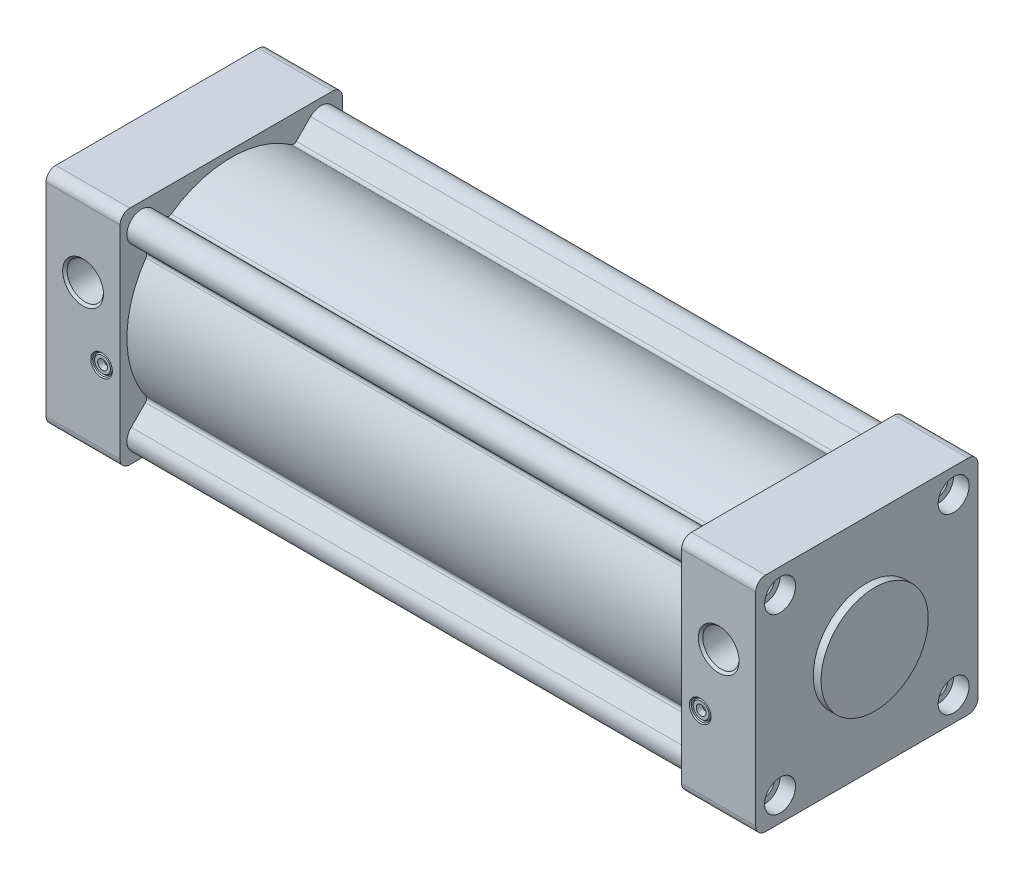
SolidWorks part; units mm, degrees
material "A3钢"
ref_plane "前视基准面" through (0, 0, 0) normal (0, 0, 1) x (1, 0, 0)
ref_plane "上视基准面" through (0, 0, 0) normal (0, 1, 0) x (1, 0, 0)
ref_plane "右视基准面" through (0, 0, 0) normal (1, 0, 0) x (0, 0, -1)
sketch "草图1" plane through (0, 0, 0) normal (1, 0, 0) x (0, 0, -1)
  line L0 (-52, -57) -> (52, -57)
  line L1 (57, -52) -> (57, 52)
  line L2 (52, 57) -> (-52, 57)
  line L3 (-57, 52) -> (-57, -52)
  arc A0 (-57, -52) -> (-52, -57) centre (-52, -52) ccw
  arc A1 (52, -57) -> (57, -52) centre (52, -52) ccw
  arc A2 (57, 52) -> (52, 57) centre (52, 52) ccw
  arc A3 (-52, 57) -> (-57, 52) centre (-52, 52) ccw
extrude "凸台-拉伸1" add sketch "草图1" along normal blind 38
sketch "草图2" plane through (0, 0, 0) normal (0, 1, 0) x (1, 0, 0)
  line L0 (-20, 0) -> (-20, 23)
  line L1 (-19, 24) -> (-5, 24)
  line L2 (-5, 24) -> (-5, 26.5)
  line L3 (-4, 27.5) -> (38, 27.5)
  line L4 (38, 27.5) -> (38, 0)
  line L5 (38, 0) -> (-20, 0)
  line L6 (38, 0) -> (-20, 0) construction
  arc A0 (-20, 23) -> (-19, 24) centre (-19, 23) cw
  arc A1 (-5, 26.5) -> (-4, 27.5) centre (-4, 26.5) cw
revolve "旋转1" add sketch "草图2" angle 360 about L6
ref_plane "基准面1" through (38, 0, 0) normal (1, 0, 0) x (0, 0, -1)
sketch "草图3" plane through (38, 0, 0) normal (1, 0, 0) x (0, 0, -1)
  line L0 (-43.9685, -33.3619) -> (-51.3033, -40.6967)
  line L1 (-40.6967, -51.3033) -> (-33.3619, -43.9685)
  line L2 (33.3619, -43.9685) -> (40.6967, -51.3033)
  line L3 (51.3033, -40.6967) -> (43.9685, -33.3619)
  line L4 (43.9685, 33.3619) -> (51.3033, 40.6967)
  line L5 (40.6967, 51.3033) -> (33.3619, 43.9685)
  line L6 (-33.3619, 43.9685) -> (-40.6967, 51.3033)
  line L7 (-51.3033, 40.6967) -> (-43.9685, 33.3619)
  arc A0 (-43.7473, 30.7964) -> (-43.7473, -30.7964) centre (0, 0) ccw
  arc A1 (-43.7473, -30.7964) -> (-43.9685, -33.3619) centre (-45.3827, -31.9477) cw
  arc A2 (-51.3033, -40.6967) -> (-40.6967, -51.3033) centre (-46, -46) ccw
  arc A3 (-33.3619, -43.9685) -> (-30.7964, -43.7473) centre (-31.9477, -45.3827) cw
  arc A4 (-30.7964, -43.7473) -> (30.7964, -43.7473) centre (0, 0) ccw
  arc A5 (30.7964, -43.7473) -> (33.3619, -43.9685) centre (31.9477, -45.3827) cw
  arc A6 (40.6967, -51.3033) -> (51.3033, -40.6967) centre (46, -46) ccw
  arc A7 (43.9685, -33.3619) -> (43.7473, -30.7964) centre (45.3827, -31.9477) cw
  arc A8 (43.7473, -30.7964) -> (43.7473, 30.7964) centre (0, 0) ccw
  arc A9 (43.7473, 30.7964) -> (43.9685, 33.3619) centre (45.3827, 31.9477) cw
  arc A10 (51.3033, 40.6967) -> (40.6967, 51.3033) centre (46, 46) ccw
  arc A11 (33.3619, 43.9685) -> (30.7964, 43.7473) centre (31.9477, 45.3827) cw
  arc A12 (30.7964, 43.7473) -> (-30.7964, 43.7473) centre (0, 0) ccw
  arc A13 (-30.7964, 43.7473) -> (-33.3619, 43.9685) centre (-31.9477, 45.3827) cw
  arc A14 (-40.6967, 51.3033) -> (-51.3033, 40.6967) centre (-46, 46) ccw
  arc A15 (-43.9685, 33.3619) -> (-43.7473, 30.7964) centre (-45.3827, 31.9477) cw
  circle A16 centre (44.5, 44.5) radius 4.35
  circle A17 centre (44.5, -44.5) radius 4.35
  circle A18 centre (-44.5, 44.5) radius 4.35
  circle A19 centre (-44.5, -44.5) radius 4.35
extrude "凸台-拉伸2" add sketch "草图3" along normal blind 288
ref_plane "基准面2" through (364, 0, 0) normal (1, 0, 0) x (0, 0, -1)
sketch "草图4" plane through (364, 0, 0) normal (1, 0, 0) x (0, 0, -1)
  line L0 (-52, -57) -> (52, -57)
  line L1 (57, -52) -> (57, 52)
  line L2 (52, 57) -> (-52, 57)
  line L3 (-57, 52) -> (-57, -52)
  arc A0 (-57, -52) -> (-52, -57) centre (-52, -52) ccw
  arc A1 (52, -57) -> (57, -52) centre (52, -52) ccw
  arc A2 (57, 52) -> (52, 57) centre (52, 52) ccw
  arc A3 (-52, 57) -> (-57, 52) centre (-52, 52) ccw
extrude "凸台-拉伸3" add sketch "草图4" against normal blind 38
sketch "草图5" plane through (0, 0, 0) normal (0, 0, 1) x (1, 0, 0)
  line L0 (326, 0) -> (326, 27.5)
  line L1 (326, 27.5) -> (368, 27.5)
  line L2 (368, 27.5) -> (368, 0)
  line L3 (368, 0) -> (326, 0)
  line L4 (368, 0) -> (326, 0) construction
revolve "旋转2" add sketch "草图5" angle 360 about L4 reverse direction yes
ref_plane "基准面3" through (0, 17, 0) normal (0, 1, 0) x (1, 0, 0)
sketch "草图6" plane through (0, 17, 0) normal (0, 1, 0) x (1, 0, 0)
  line L0 (19, -57) -> (8.5225, -57)
  line L1 (8.5225, -57) -> (9.6845, -55.838)
  line L2 (9.6845, -55.838) -> (9.6845, -35)
  line L3 (9.6845, -35) -> (19, -29.6217)
  line L4 (19, -29.6217) -> (19, -57)
  line L5 (19, -29.6217) -> (19, -57) construction
revolve "切除-旋转1" cut sketch "草图6" angle 360 about L5 reverse direction yes
cosmetic thread "装饰螺纹线1" parameters "D1"=20, "D2"=20.955
sketch "草图7" plane through (0, 17, 0) normal (0, 1, 0) x (1, 0, 0)
  line L0 (345, -57) -> (334.5225, -57)
  line L1 (334.5225, -57) -> (335.6845, -55.838)
  line L2 (335.6845, -55.838) -> (335.6845, -35)
  line L3 (335.6845, -35) -> (345, -29.6217)
  line L4 (345, -29.6217) -> (345, -57)
  line L5 (345, -29.6217) -> (345, -57) construction
revolve "切除-旋转2" cut sketch "草图7" angle 360 about L5 reverse direction yes
cosmetic thread "装饰螺纹线2" parameters "D1"=20, "D2"=20.955
ref_plane "基准面4" through (0, -17, 0) normal (0, 1, 0) x (1, 0, 0)
ref_plane "基准面5" through (0, -15, 0) normal (0, 1, 0) x (1, 0, 0)
sketch "草图8" plane through (0, -15, 0) normal (0, 1, 0) x (1, 0, 0)
  line L0 (28.5, -57) -> (22.95, -57)
  line L1 (22.95, -57) -> (23.45, -56.5)
  line L2 (23.45, -56.5) -> (23.45, -53.5)
  line L3 (23.45, -53.5) -> (23.95, -53.5)
  line L4 (23.95, -53.5) -> (23.95, -56)
  line L5 (23.95, -56) -> (24.45, -56.5)
  line L6 (24.45, -56.5) -> (26, -56.5)
  line L7 (26, -56.5) -> (26, -53.5)
  line L8 (26, -53.5) -> (28.5, -53.5)
  line L9 (28.5, -53.5) -> (28.5, -57)
  line L10 (28.5, -53.5) -> (28.5, -57) construction
revolve "切除-旋转3" cut sketch "草图8" angle 360 about L10 reverse direction yes
sketch "草图9" plane through (0, -15, 0) normal (0, 1, 0) x (1, 0, 0)
  line L0 (335.5, -57) -> (329.95, -57)
  line L1 (329.95, -57) -> (330.45, -56.5)
  line L2 (330.45, -56.5) -> (330.45, -53.5)
  line L3 (330.45, -53.5) -> (330.95, -53.5)
  line L4 (330.95, -53.5) -> (330.95, -56)
  line L5 (330.95, -56) -> (331.45, -56.5)
  line L6 (331.45, -56.5) -> (333, -56.5)
  line L7 (333, -56.5) -> (333, -53.5)
  line L8 (333, -53.5) -> (335.5, -53.5)
  line L9 (335.5, -53.5) -> (335.5, -57)
  line L10 (335.5, -53.5) -> (335.5, -57) construction
revolve "切除-旋转4" cut sketch "草图9" angle 360 about L10 reverse direction yes
ref_plane "基准面6" through (0, 15, 0) normal (0, 1, 0) x (1, 0, 0)
ref_plane "基准面7" through (0, 0, -44.5) normal (0, 0, 1) x (1, 0, 0)
sketch "草图10" plane through (0, 0, -44.5) normal (0, 0, 1) x (1, 0, 0)
  line L0 (22, -44.5) -> (22, -48.688)
  line L1 (22, -48.688) -> (8.812, -48.688)
  line L2 (8.812, -48.688) -> (8, -49.5)
  line L3 (8, -49.5) -> (8, -52.45)
  line L4 (8, -52.45) -> (0, -52.45)
  line L5 (0, -52.45) -> (0, -44.5)
  line L6 (0, -44.5) -> (22, -44.5)
  line L7 (0, -44.5) -> (22, -44.5) construction
revolve "切除-旋转5" cut sketch "草图10" angle 360 about L7 reverse direction yes
cosmetic thread "装饰螺纹线3" parameters "D1"=14, "D2"=10
sketch "草图11" plane through (0, 0, 0) normal (1, 0, 0) x (0, 0, -1)
  line L0 (44.5, -44.5) -> (44.5, 44.5)
  line L1 (44.5, -44.5) -> (-44.5, -44.5)
pattern_linear "阵列(线性)1" count 2 spacing 89 along (0, 1, 0) count 2 spacing 89 along (0, 0, 1) of "切除-旋转5"
sketch "草图12" plane through (0, 0, -44.5) normal (0, 0, 1) x (1, 0, 0)
  line L0 (364, -44.5) -> (364, -52.45)
  line L1 (364, -52.45) -> (356, -52.45)
  line L2 (356, -52.45) -> (356, -49.5)
  line L3 (356, -49.5) -> (355.188, -48.688)
  line L4 (355.188, -48.688) -> (342, -48.688)
  line L5 (342, -48.688) -> (342, -44.5)
  line L6 (342, -44.5) -> (364, -44.5)
  line L7 (342, -44.5) -> (364, -44.5) construction
revolve "切除-旋转6" cut sketch "草图12" angle 360 about L7 reverse direction yes
cosmetic thread "装饰螺纹线4" parameters "D1"=14, "D2"=10
sketch "草图13" plane through (364, 0, 0) normal (1, 0, 0) x (0, 0, -1)
  line L0 (44.5, -44.5) -> (44.5, 44.5)
  line L1 (44.5, -44.5) -> (-44.5, -44.5)
pattern_linear "阵列(线性)2" count 2 spacing 89 along (0, 1, 0) count 2 spacing 89 along (0, 0, 1) of "切除-旋转6"
sketch "草图14" plane through (0, 0, 0) normal (0, 0, 1) x (1, 0, 0)
  line L0 (-20, 0) -> (-20, 15)
  line L1 (-20, 15) -> (-1, 15)
  line L2 (-1, 15) -> (-1, 18.2)
  line L3 (-1, 18.2) -> (35, 18.2)
  line L4 (35, 18.2) -> (35, 50)
  line L5 (35, 50) -> (329, 50)
  line L6 (329, 50) -> (329, 18.2)
  line L7 (329, 18.2) -> (365, 18.2)
  line L8 (365, 18.2) -> (365, 0)
  line L9 (365, 0) -> (-20, 0)
  line L10 (365, 0) -> (-20, 0) construction
revolve "切除-旋转7" cut sketch "草图14" angle 360 about L10 reverse direction yes
ref_plane "基准面8" through (31.5, 0, 0) normal (1, 0, 0) x (0, 0, -1)
ref_plane "基准面9" through (332.5, 0, 0) normal (1, 0, 0) x (0, 0, -1)
ref_plane "基准面10" through (0, 0, 57) normal (0, 0, 1) x (1, 0, 0)
ref_plane "基准面11" through (364, 0, 0) normal (1, 0, 0) x (0, 0, -1)
ref_plane "基准面12" through (182, 0, 0) normal (1, 0, 0) x (0, 0, -1)
ref_plane "基准面13" through (39, 0, 0) normal (1, 0, 0) x (0, 0, -1)
ref_plane "基准面14" through (325, 0, 0) normal (1, 0, 0) x (0, 0, -1)
ref_plane "IP_CA_SCREW 1 XY" through (0, 0, 0) normal (-1, 0, 0) x (0, 0, 1)
ref_plane "IP_CA_SCREW 1 XZ" through (0, -44.5, 0) normal (0, 1, 0) x (1, 0, 0)
ref_plane "IP_CA_SCREW 1 YZ" through (0, 0, 44.5) normal (0, 0, -1) x (-1, 0, 0)
ref_axis "IP_CA_SCREW 1 X" through (0, -44.5, 80.9) along (0, 0, -1)
ref_axis "IP_CA_SCREW 1 Y" through (0, 50, 44.5) along (0, -1, 0)
ref_axis "IP_CA_SCREW 1 Z" through (-80.9, -44.5, 44.5) along (1, 0, 0)
sketch3d "IP_CA_SCREW 1"
  point P0 (0, -44.5, 44.5)
ref_plane "IP_CA_SCREW 2 XY" through (0, 0, 0) normal (-1, 0, 0) x (0, 0, 1)
ref_plane "IP_CA_SCREW 2 XZ" through (0, -44.5, 0) normal (0, 1, 0) x (1, 0, 0)
ref_plane "IP_CA_SCREW 2 YZ" through (0, 0, -44.5) normal (0, 0, -1) x (-1, 0, 0)
ref_axis "IP_CA_SCREW 2 X" through (0, -44.5, 80.9) along (0, 0, -1)
ref_axis "IP_CA_SCREW 2 Y" through (0, 50, -44.5) along (0, -1, 0)
ref_axis "IP_CA_SCREW 2 Z" through (-80.9, -44.5, -44.5) along (1, 0, 0)
sketch3d "IP_CA_SCREW 2"
  point P0 (0, -44.5, -44.5)
ref_plane "IP_CA_SCREW 3 XY" through (0, 0, 0) normal (-1, 0, 0) x (0, 0, 1)
ref_plane "IP_CA_SCREW 3 XZ" through (0, 44.5, 0) normal (0, 1, 0) x (1, 0, 0)
ref_plane "IP_CA_SCREW 3 YZ" through (0, 0, 44.5) normal (0, 0, -1) x (-1, 0, 0)
ref_axis "IP_CA_SCREW 3 X" through (0, 44.5, 80.9) along (0, 0, -1)
ref_axis "IP_CA_SCREW 3 Y" through (0, 50, 44.5) along (0, -1, 0)
ref_axis "IP_CA_SCREW 3 Z" through (-80.9, 44.5, 44.5) along (1, 0, 0)
sketch3d "IP_CA_SCREW 3"
  point P0 (0, 44.5, 44.5)
ref_plane "IP_CA_SCREW 4 XY" through (0, 0, 0) normal (-1, 0, 0) x (0, 0, 1)
ref_plane "IP_CA_SCREW 4 XZ" through (0, 44.5, 0) normal (0, 1, 0) x (1, 0, 0)
ref_plane "IP_CA_SCREW 4 YZ" through (0, 0, -44.5) normal (0, 0, -1) x (-1, 0, 0)
ref_axis "IP_CA_SCREW 4 X" through (0, 44.5, 80.9) along (0, 0, -1)
ref_axis "IP_CA_SCREW 4 Y" through (0, 50, -44.5) along (0, -1, 0)
ref_axis "IP_CA_SCREW 4 Z" through (-80.9, 44.5, -44.5) along (1, 0, 0)
sketch3d "IP_CA_SCREW 4"
  point P0 (0, 44.5, -44.5)
ref_plane "IP_CA_SCREW_2 1 XY" through (364, 0, 0) normal (1, 0, 0) x (0, 0, -1)
ref_plane "IP_CA_SCREW_2 1 XZ" through (0, -44.5, 0) normal (0, -1, 0) x (-1, 0, 0)
ref_plane "IP_CA_SCREW_2 1 YZ" through (0, 0, 44.5) normal (0, 0, -1) x (-1, 0, 0)
ref_axis "IP_CA_SCREW_2 1 X" through (364, -44.5, 80.9) along (0, 0, -1)
ref_axis "IP_CA_SCREW_2 1 Y" through (364, -50, 44.5) along (0, 1, 0)
ref_axis "IP_CA_SCREW_2 1 Z" through (80.9, -44.5, 44.5) along (-1, 0, 0)
sketch3d "IP_CA_SCREW_2 1"
  point P0 (364, -44.5, 44.5)
ref_plane "IP_CA_SCREW_2 2 XY" through (364, 0, 0) normal (1, 0, 0) x (0, 0, -1)
ref_plane "IP_CA_SCREW_2 2 XZ" through (0, -44.5, 0) normal (0, -1, 0) x (-1, 0, 0)
ref_plane "IP_CA_SCREW_2 2 YZ" through (0, 0, -44.5) normal (0, 0, -1) x (-1, 0, 0)
ref_axis "IP_CA_SCREW_2 2 X" through (364, -44.5, 80.9) along (0, 0, -1)
ref_axis "IP_CA_SCREW_2 2 Y" through (364, -50, -44.5) along (0, 1, 0)
ref_axis "IP_CA_SCREW_2 2 Z" through (80.9, -44.5, -44.5) along (-1, 0, 0)
sketch3d "IP_CA_SCREW_2 2"
  point P0 (364, -44.5, -44.5)
ref_plane "IP_CA_SCREW_2 3 XY" through (364, 0, 0) normal (1, 0, 0) x (0, 0, -1)
ref_plane "IP_CA_SCREW_2 3 XZ" through (0, 44.5, 0) normal (0, -1, 0) x (-1, 0, 0)
ref_plane "IP_CA_SCREW_2 3 YZ" through (0, 0, 44.5) normal (0, 0, -1) x (-1, 0, 0)
ref_axis "IP_CA_SCREW_2 3 X" through (364, 44.5, 80.9) along (0, 0, -1)
ref_axis "IP_CA_SCREW_2 3 Y" through (364, -50, 44.5) along (0, 1, 0)
ref_axis "IP_CA_SCREW_2 3 Z" through (80.9, 44.5, 44.5) along (-1, 0, 0)
sketch3d "IP_CA_SCREW_2 3"
  point P0 (364, 44.5, 44.5)
ref_plane "IP_CA_SCREW_2 4 XY" through (364, 0, 0) normal (1, 0, 0) x (0, 0, -1)
ref_plane "IP_CA_SCREW_2 4 XZ" through (0, 44.5, 0) normal (0, -1, 0) x (-1, 0, 0)
ref_plane "IP_CA_SCREW_2 4 YZ" through (0, 0, -44.5) normal (0, 0, -1) x (-1, 0, 0)
ref_axis "IP_CA_SCREW_2 4 X" through (364, 44.5, 80.9) along (0, 0, -1)
ref_axis "IP_CA_SCREW_2 4 Y" through (364, -50, -44.5) along (0, 1, 0)
ref_axis "IP_CA_SCREW_2 4 Z" through (80.9, 44.5, -44.5) along (-1, 0, 0)
sketch3d "IP_CA_SCREW_2 4"
  point P0 (364, 44.5, -44.5)
ref_plane "IP_CH 1 XY" through (0, 0, 57) normal (0, 0, 1) x (1, 0, 0)
ref_plane "IP_CH 1 XZ" through (0, -15, 0) normal (0, -1, 0) x (-1, 0, 0)
ref_plane "IP_CH 1 YZ" through (28.5, 0, 0) normal (1, 0, 0) x (0, 0, -1)
ref_axis "IP_CH 1 X" through (-80.9, -15, 57) along (1, 0, 0)
ref_axis "IP_CH 1 Y" through (28.5, -50, 57) along (0, 1, 0)
ref_axis "IP_CH 1 Z" through (28.5, -15, 80.9) along (0, 0, -1)
sketch3d "IP_CH 1"
  point P0 (28.5, -15, 57)
ref_plane "IP_CH 2 XY" through (0, 0, 57) normal (0, 0, 1) x (1, 0, 0)
ref_plane "IP_CH 2 XZ" through (0, -15, 0) normal (0, -1, 0) x (-1, 0, 0)
ref_plane "IP_CH 2 YZ" through (335.5, 0, 0) normal (1, 0, 0) x (0, 0, -1)
ref_axis "IP_CH 2 X" through (-80.9, -15, 57) along (1, 0, 0)
ref_axis "IP_CH 2 Y" through (335.5, -50, 57) along (0, 1, 0)
ref_axis "IP_CH 2 Z" through (335.5, -15, 80.9) along (0, 0, -1)
sketch3d "IP_CH 2"
  point P0 (335.5, -15, 57)
ref_plane "IP_DUMMY XY" through (0, 0, 0) normal (-1, 0, 0) x (0, 0, 1)
ref_plane "IP_DUMMY XZ" through (0, 0, 0) normal (0, 1, 0) x (1, 0, 0)
ref_plane "IP_DUMMY YZ" through (0, 0, 0) normal (0, 0, -1) x (-1, 0, 0)
ref_axis "IP_DUMMY X" through (0, 0, 80.9) along (0, 0, -1)
ref_axis "IP_DUMMY Y" through (0, 50, 0) along (0, -1, 0)
ref_axis "IP_DUMMY Z" through (-80.9, 0, 0) along (1, 0, 0)
sketch3d "IP_DUMMY"
  point P0 (0, 0, 0)
ref_plane "IP_LB XY" through (0, 0, 0) normal (-1, 0, 0) x (0, 0, 1)
ref_plane "IP_LB XZ" through (0, 0, 0) normal (0, 1, 0) x (1, 0, 0)
ref_plane "IP_LB YZ" through (0, 0, 0) normal (0, 0, -1) x (-1, 0, 0)
ref_axis "IP_LB X" through (0, 0, 80.9) along (0, 0, -1)
ref_axis "IP_LB Y" through (0, 50, 0) along (0, -1, 0)
ref_axis "IP_LB Z" through (-80.9, 0, 0) along (1, 0, 0)
sketch3d "IP_LB"
  point P0 (0, 0, 0)
ref_plane "IP_LB_2 XY" through (364, 0, 0) normal (1, 0, 0) x (0, 0, -1)
ref_plane "IP_LB_2 XZ" through (0, 0, 0) normal (0, -1, 0) x (-1, 0, 0)
ref_plane "IP_LB_2 YZ" through (0, 0, 0) normal (0, 0, -1) x (-1, 0, 0)
ref_axis "IP_LB_2 X" through (364, 0, 80.9) along (0, 0, -1)
ref_axis "IP_LB_2 Y" through (364, -50, 0) along (0, 1, 0)
ref_axis "IP_LB_2 Z" through (80.9, 0, 0) along (-1, 0, 0)
sketch3d "IP_LB_2"
  point P0 (364, 0, 0)
ref_plane "IP_LB_SCREW 1 XY" through (0, 0, 0) normal (-1, 0, 0) x (0, 0, 1)
ref_plane "IP_LB_SCREW 1 XZ" through (0, -44.5, 0) normal (0, 1, 0) x (1, 0, 0)
ref_plane "IP_LB_SCREW 1 YZ" through (0, 0, 44.5) normal (0, 0, -1) x (-1, 0, 0)
ref_axis "IP_LB_SCREW 1 X" through (0, -44.5, 80.9) along (0, 0, -1)
ref_axis "IP_LB_SCREW 1 Y" through (0, 50, 44.5) along (0, -1, 0)
ref_axis "IP_LB_SCREW 1 Z" through (-80.9, -44.5, 44.5) along (1, 0, 0)
sketch3d "IP_LB_SCREW 1"
  point P0 (0, -44.5, 44.5)
ref_plane "IP_LB_SCREW 2 XY" through (0, 0, 0) normal (-1, 0, 0) x (0, 0, 1)
ref_plane "IP_LB_SCREW 2 XZ" through (0, -44.5, 0) normal (0, 1, 0) x (1, 0, 0)
ref_plane "IP_LB_SCREW 2 YZ" through (0, 0, -44.5) normal (0, 0, -1) x (-1, 0, 0)
ref_axis "IP_LB_SCREW 2 X" through (0, -44.5, 80.9) along (0, 0, -1)
ref_axis "IP_LB_SCREW 2 Y" through (0, 50, -44.5) along (0, -1, 0)
ref_axis "IP_LB_SCREW 2 Z" through (-80.9, -44.5, -44.5) along (1, 0, 0)
sketch3d "IP_LB_SCREW 2"
  point P0 (0, -44.5, -44.5)
ref_plane "IP_LB_SCREW_2 1 XY" through (364, 0, 0) normal (1, 0, 0) x (0, 0, -1)
ref_plane "IP_LB_SCREW_2 1 XZ" through (0, -44.5, 0) normal (0, -1, 0) x (-1, 0, 0)
ref_plane "IP_LB_SCREW_2 1 YZ" through (0, 0, 44.5) normal (0, 0, -1) x (-1, 0, 0)
ref_axis "IP_LB_SCREW_2 1 X" through (364, -44.5, 80.9) along (0, 0, -1)
ref_axis "IP_LB_SCREW_2 1 Y" through (364, -50, 44.5) along (0, 1, 0)
ref_axis "IP_LB_SCREW_2 1 Z" through (80.9, -44.5, 44.5) along (-1, 0, 0)
sketch3d "IP_LB_SCREW_2 1"
  point P0 (364, -44.5, 44.5)
ref_plane "IP_LB_SCREW_2 2 XY" through (364, 0, 0) normal (1, 0, 0) x (0, 0, -1)
ref_plane "IP_LB_SCREW_2 2 XZ" through (0, -44.5, 0) normal (0, -1, 0) x (-1, 0, 0)
ref_plane "IP_LB_SCREW_2 2 YZ" through (0, 0, -44.5) normal (0, 0, -1) x (-1, 0, 0)
ref_axis "IP_LB_SCREW_2 2 X" through (364, -44.5, 80.9) along (0, 0, -1)
ref_axis "IP_LB_SCREW_2 2 Y" through (364, -50, -44.5) along (0, 1, 0)
ref_axis "IP_LB_SCREW_2 2 Z" through (80.9, -44.5, -44.5) along (-1, 0, 0)
sketch3d "IP_LB_SCREW_2 2"
  point P0 (364, -44.5, -44.5)
ref_plane "IP_ROD XY" through (0, 0, 0) normal (-1, 0, 0) x (0, 0, 1)
ref_plane "IP_ROD XZ" through (0, 0, 0) normal (0, 1, 0) x (1, 0, 0)
ref_plane "IP_ROD YZ" through (0, 0, 0) normal (0, 0, -1) x (-1, 0, 0)
ref_axis "IP_ROD X" through (0, 0, 80.9) along (0, 0, -1)
ref_axis "IP_ROD Y" through (0, 50, 0) along (0, -1, 0)
ref_axis "IP_ROD Z" through (-80.9, 0, 0) along (1, 0, 0)
sketch3d "IP_ROD"
  point P0 (0, 0, 0)
ref_plane "IP_SCREW 1 XY" through (31.5, 0, 0) normal (-1, 0, 0) x (0, 0, 1)
ref_plane "IP_SCREW 1 XZ" through (0, -44.5, 0) normal (0, 1, 0) x (1, 0, 0)
ref_plane "IP_SCREW 1 YZ" through (0, 0, 44.5) normal (0, 0, -1) x (-1, 0, 0)
ref_axis "IP_SCREW 1 X" through (31.5, -44.5, 80.9) along (0, 0, -1)
ref_axis "IP_SCREW 1 Y" through (31.5, 50, 44.5) along (0, -1, 0)
ref_axis "IP_SCREW 1 Z" through (-80.9, -44.5, 44.5) along (1, 0, 0)
sketch3d "IP_SCREW 1"
  point P0 (31.5, -44.5, 44.5)
ref_plane "IP_SCREW 2 XY" through (31.5, 0, 0) normal (-1, 0, 0) x (0, 0, 1)
ref_plane "IP_SCREW 2 XZ" through (0, -44.5, 0) normal (0, 1, 0) x (1, 0, 0)
ref_plane "IP_SCREW 2 YZ" through (0, 0, -44.5) normal (0, 0, -1) x (-1, 0, 0)
ref_axis "IP_SCREW 2 X" through (31.5, -44.5, 80.9) along (0, 0, -1)
ref_axis "IP_SCREW 2 Y" through (31.5, 50, -44.5) along (0, -1, 0)
ref_axis "IP_SCREW 2 Z" through (-80.9, -44.5, -44.5) along (1, 0, 0)
sketch3d "IP_SCREW 2"
  point P0 (31.5, -44.5, -44.5)
ref_plane "IP_SCREW 3 XY" through (31.5, 0, 0) normal (-1, 0, 0) x (0, 0, 1)
ref_plane "IP_SCREW 3 XZ" through (0, 44.5, 0) normal (0, 1, 0) x (1, 0, 0)
ref_plane "IP_SCREW 3 YZ" through (0, 0, 44.5) normal (0, 0, -1) x (-1, 0, 0)
ref_axis "IP_SCREW 3 X" through (31.5, 44.5, 80.9) along (0, 0, -1)
ref_axis "IP_SCREW 3 Y" through (31.5, 50, 44.5) along (0, -1, 0)
ref_axis "IP_SCREW 3 Z" through (-80.9, 44.5, 44.5) along (1, 0, 0)
sketch3d "IP_SCREW 3"
  point P0 (31.5, 44.5, 44.5)
ref_plane "IP_SCREW 4 XY" through (31.5, 0, 0) normal (-1, 0, 0) x (0, 0, 1)
ref_plane "IP_SCREW 4 XZ" through (0, 44.5, 0) normal (0, 1, 0) x (1, 0, 0)
ref_plane "IP_SCREW 4 YZ" through (0, 0, -44.5) normal (0, 0, -1) x (-1, 0, 0)
ref_axis "IP_SCREW 4 X" through (31.5, 44.5, 80.9) along (0, 0, -1)
ref_axis "IP_SCREW 4 Y" through (31.5, 50, -44.5) along (0, -1, 0)
ref_axis "IP_SCREW 4 Z" through (-80.9, 44.5, -44.5) along (1, 0, 0)
sketch3d "IP_SCREW 4"
  point P0 (31.5, 44.5, -44.5)
ref_plane "IP_SCREW_2 1 XY" through (332.5, 0, 0) normal (1, 0, 0) x (0, 0, -1)
ref_plane "IP_SCREW_2 1 XZ" through (0, -44.5, 0) normal (0, -1, 0) x (-1, 0, 0)
ref_plane "IP_SCREW_2 1 YZ" through (0, 0, 44.5) normal (0, 0, -1) x (-1, 0, 0)
ref_axis "IP_SCREW_2 1 X" through (332.5, -44.5, 80.9) along (0, 0, -1)
ref_axis "IP_SCREW_2 1 Y" through (332.5, -50, 44.5) along (0, 1, 0)
ref_axis "IP_SCREW_2 1 Z" through (80.9, -44.5, 44.5) along (-1, 0, 0)
sketch3d "IP_SCREW_2 1"
  point P0 (332.5, -44.5, 44.5)
ref_plane "IP_SCREW_2 2 XY" through (332.5, 0, 0) normal (1, 0, 0) x (0, 0, -1)
ref_plane "IP_SCREW_2 2 XZ" through (0, -44.5, 0) normal (0, -1, 0) x (-1, 0, 0)
ref_plane "IP_SCREW_2 2 YZ" through (0, 0, -44.5) normal (0, 0, -1) x (-1, 0, 0)
ref_axis "IP_SCREW_2 2 X" through (332.5, -44.5, 80.9) along (0, 0, -1)
ref_axis "IP_SCREW_2 2 Y" through (332.5, -50, -44.5) along (0, 1, 0)
ref_axis "IP_SCREW_2 2 Z" through (80.9, -44.5, -44.5) along (-1, 0, 0)
sketch3d "IP_SCREW_2 2"
  point P0 (332.5, -44.5, -44.5)
ref_plane "IP_SCREW_2 3 XY" through (332.5, 0, 0) normal (1, 0, 0) x (0, 0, -1)
ref_plane "IP_SCREW_2 3 XZ" through (0, 44.5, 0) normal (0, -1, 0) x (-1, 0, 0)
ref_plane "IP_SCREW_2 3 YZ" through (0, 0, 44.5) normal (0, 0, -1) x (-1, 0, 0)
ref_axis "IP_SCREW_2 3 X" through (332.5, 44.5, 80.9) along (0, 0, -1)
ref_axis "IP_SCREW_2 3 Y" through (332.5, -50, 44.5) along (0, 1, 0)
ref_axis "IP_SCREW_2 3 Z" through (80.9, 44.5, 44.5) along (-1, 0, 0)
sketch3d "IP_SCREW_2 3"
  point P0 (332.5, 44.5, 44.5)
ref_plane "IP_SCREW_2 4 XY" through (332.5, 0, 0) normal (1, 0, 0) x (0, 0, -1)
ref_plane "IP_SCREW_2 4 XZ" through (0, 44.5, 0) normal (0, -1, 0) x (-1, 0, 0)
ref_plane "IP_SCREW_2 4 YZ" through (0, 0, -44.5) normal (0, 0, -1) x (-1, 0, 0)
ref_axis "IP_SCREW_2 4 X" through (332.5, 44.5, 80.9) along (0, 0, -1)
ref_axis "IP_SCREW_2 4 Y" through (332.5, -50, -44.5) along (0, 1, 0)
ref_axis "IP_SCREW_2 4 Z" through (80.9, 44.5, -44.5) along (-1, 0, 0)
sketch3d "IP_SCREW_2 4"
  point P0 (332.5, 44.5, -44.5)
ref_plane "IP_SWITCH1 XY" through (39, 0, 0) normal (-1, 0, 0) x (0, 0, 1)
ref_plane "IP_SWITCH1 XZ" through (0, -46, 0) normal (0, 1, 0) x (1, 0, 0)
ref_plane "IP_SWITCH1 YZ" through (0, 0, 46) normal (0, 0, -1) x (-1, 0, 0)
ref_axis "IP_SWITCH1 X" through (39, -46, 80.9) along (0, 0, -1)
ref_axis "IP_SWITCH1 Y" through (39, 50, 46) along (0, -1, 0)
ref_axis "IP_SWITCH1 Z" through (-80.9, -46, 46) along (1, 0, 0)
sketch3d "IP_SWITCH1"
  point P0 (39, -46, 46)
ref_plane "IP_SWITCH2 XY" through (325, 0, 0) normal (1, 0, 0) x (0, 0, -1)
ref_plane "IP_SWITCH2 XZ" through (0, 46, 0) normal (0, -1, 0) x (-1, 0, 0)
ref_plane "IP_SWITCH2 YZ" through (0, 0, 46) normal (0, 0, -1) x (-1, 0, 0)
ref_axis "IP_SWITCH2 X" through (325, 46, 80.9) along (0, 0, -1)
ref_axis "IP_SWITCH2 Y" through (325, -50, 46) along (0, 1, 0)
ref_axis "IP_SWITCH2 Z" through (80.9, 46, 46) along (-1, 0, 0)
sketch3d "IP_SWITCH2"
  point P0 (325, 46, 46)
ref_plane "IP_TC XY" through (182, 0, 0) normal (1, 0, 0) x (0, 0, -1)
ref_plane "IP_TC XZ" through (0, 0, 0) normal (0, -1, 0) x (-1, 0, 0)
ref_plane "IP_TC YZ" through (0, 0, 0) normal (0, 0, -1) x (-1, 0, 0)
ref_axis "IP_TC X" through (182, 0, 80.9) along (0, 0, -1)
ref_axis "IP_TC Y" through (182, -50, 0) along (0, 1, 0)
ref_axis "IP_TC Z" through (80.9, 0, 0) along (-1, 0, 0)
sketch3d "IP_TC"
  point P0 (182, 0, 0)
